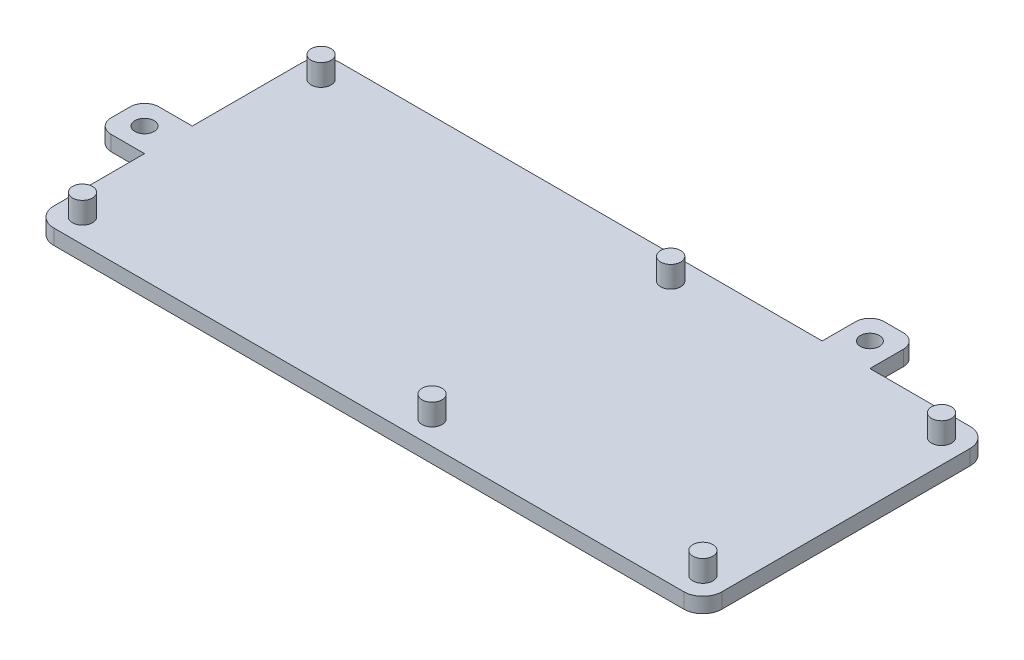
SolidWorks part; units mm, degrees
material "Custom Plastic"
ref_plane "X-Y Datum" through (0, 0, 0) normal (0, 0, 1) x (1, 0, 0)
ref_plane "X-Z Datum" through (0, 0, 0) normal (0, 1, 0) x (1, 0, 0)
ref_plane "Y-Z Datum" through (0, 0, 0) normal (1, 0, 0) x (0, 0, -1)
sketch "Sketch1" plane through (0, -38.0633, 0) normal (0, -1, 0) x (1, 0, 0)
  circle A0 centre (-181.8399, -5.7269) radius 2.0955 construction
  circle A1 centre (-108.5899, -5.7269) radius 2.0955 construction
  circle A2 centre (-51.8399, -5.7269) radius 2.0955 construction
  circle A3 centre (-51.8399, 44.2731) radius 2.0955 construction
  circle A4 centre (-108.5899, 44.2731) radius 2.0955 construction
  circle A5 centre (-181.8399, 44.2731) radius 2.0955 construction
  circle A6 centre (-181.8399, -5.7269) radius 2.0955
  circle A7 centre (-108.5899, -5.7269) radius 2.0955
  circle A8 centre (-51.8399, -5.7269) radius 2.0955
  circle A9 centre (-51.8399, 44.2731) radius 2.0955
  circle A10 centre (-108.5899, 44.2731) radius 2.0955
  circle A11 centre (-181.8399, 44.2731) radius 2.0955
extrude "Boss-Extrude1" add sketch "Sketch1" along normal blind 4.5
sketch "Sketch2" plane through (0, -42.5633, 0) normal (0, -1, 0) x (1, 0, 0)
  line L0 (-186.8399, 19.2731) -> (-46.8399, 19.2731) construction
  line L1 (-186.8399, -10.7269) -> (-186.8399, 49.2731) construction
  line L2 (-46.8399, -10.7269) -> (-46.8399, 49.2731) construction
  line L3 (-116.8399, 49.2731) -> (-116.8399, -10.7269) construction
  line L4 (-186.8399, 49.2731) -> (-46.8399, 49.2731) construction
  line L5 (-186.8399, -10.7269) -> (-46.8399, -10.7269) construction
  line L7 (-186.8399, -10.7269) -> (-46.8399, -10.7269)
  line L8 (-186.8399, -10.7269) -> (-186.8399, 49.2731)
  line L9 (-186.8399, 49.2731) -> (-46.8399, 49.2731)
  line L10 (-46.8399, -10.7269) -> (-46.8399, 49.2731)
  line L11 (-186.8399, -10.7269) -> (-46.8399, 49.2731) construction
  line L12 (-186.8399, 49.2731) -> (-46.8399, -10.7269) construction
  point P12 (-116.8399, 19.2731)
extrude "Boss-Extrude2" add sketch "Sketch2" along normal blind 3.175
fillet "Fillet1" radius 4 4 edges at (-46.8399, -44.1508, -10.7269) (-46.8399, -44.1508, 49.2731) (-186.8399, -44.1508, -10.7269) (-186.8399, -44.1508, 49.2731)
sketch "Sketch3" plane through (0, -45.7383, 0) normal (0, -1, 0) x (1, 0, 0)
  line L6 (-186.8399, 45.2731) -> (-186.8399, -6.7269) construction
  line L11 (-186.8399, 16.2731) -> (-196.8399, 16.2731)
  line L13 (-186.8399, 16.2731) -> (-186.8399, 26.2731)
  line L14 (-182.8399, -10.7269) -> (-50.8399, -10.7269) construction
  line L15 (-71.8399, -10.7269) -> (-81.8399, -10.7269)
  line L16 (-71.8399, -10.7269) -> (-71.8399, -20.7269)
  line L17 (-71.8399, -20.7269) -> (-81.8399, -20.7269)
  line L18 (-81.8399, -10.7269) -> (-81.8399, -20.7269)
  line L19 (-46.8399, -10.7269) -> (-46.8399, 49.2731) construction
  line L20 (-186.8399, 26.2731) -> (-196.8399, 26.2731)
  line L21 (-196.8399, 16.2731) -> (-196.8399, 26.2731)
  line L22 (-81.8399, -15.7269) -> (-71.8399, -15.7269) construction
  line L23 (-76.8399, -20.7269) -> (-76.8399, -10.7269) construction
  line L24 (-50.8399, 49.2731) -> (-182.8399, 49.2731) construction
  line L25 (-186.8399, 21.2731) -> (-196.8399, 21.2731) construction
  circle A1 centre (-76.8399, -15.7269) radius 2
  circle A2 centre (-191.8399, 21.2731) radius 2
  dimension "D7" = 4
  dimension "D8" = 4
  dimension "D1" = 23
  dimension "D2" = 10
  dimension "D3" = 10
  dimension "D4" = 10
  dimension "D5" = 10
  dimension "D6" = 25
extrude "Boss-Extrude3" add sketch "Sketch3" against normal blind 3.175
fillet "Fillet3" radius 3 2 edges at (-81.8399, -44.1508, -20.7269) (-71.8399, -44.1508, -20.7269)
fillet "Fillet4" radius 3 2 edges at (-196.8399, -44.1508, 26.2731) (-196.8399, -44.1508, 16.2731)
